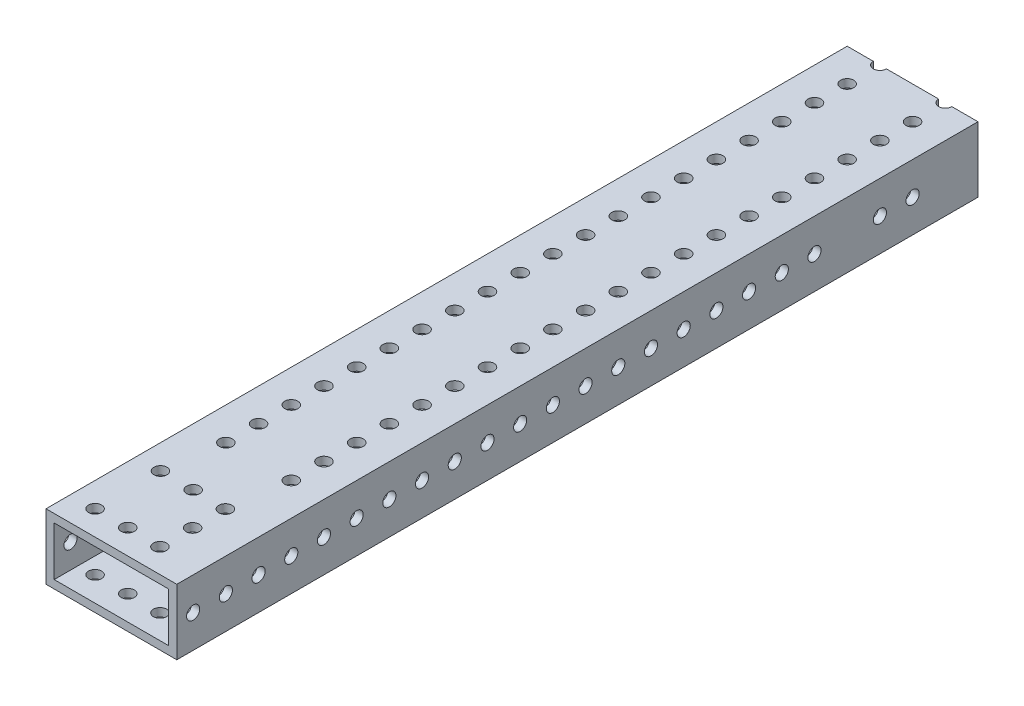
SolidWorks part; units mm, degrees
material "6061-T6 (SS)"
ref_plane "Front Plane" through (0, 0, 0) normal (0, 0, 1) x (1, 0, 0)
ref_plane "Top Plane" through (0, 0, 0) normal (0, 1, 0) x (1, 0, 0)
ref_plane "Right Plane" through (0, 0, 0) normal (1, 0, 0) x (0, 0, -1)
sketch "Sketch1" plane through (0, 0, 0) normal (0, 0, 1) x (1, 0, 0)
  line L0 (-22.225, 9.525) -> (22.225, 9.525)
  line L1 (-25.4, 12.7) -> (25.4, 12.7)
  line L2 (-25.4, 12.7) -> (-25.4, -12.7)
  line L3 (-25.4, -12.7) -> (25.4, -12.7)
  line L4 (25.4, 12.7) -> (25.4, -12.7)
  line L5 (22.225, 9.525) -> (22.225, -9.525)
  line L6 (-22.225, -9.525) -> (22.225, -9.525)
  line L7 (-22.225, 9.525) -> (-22.225, -9.525)
  line L8 (-25.4, 12.7) -> (25.4, -12.7) construction
  line L9 (25.4, 12.7) -> (-25.4, -12.7) construction
  point P5 (0, 0)
  dimension "D1" = 50.8
  dimension "D2" = 25.4
  dimension "D3" = 3.175
extrude "Boss-Extrude1" add sketch "Sketch1" along normal mid plane 469.9
sketch "Sketch5" plane through (-25.4, 0, 0) normal (-1, 0, 0) x (0, 0, 1)
  line L0 (234.95, -12.7) -> (-234.95, -12.7) construction
  line L1 (-234.95, 12.7) -> (-171.45, 12.7)
  line L2 (-234.95, 12.7) -> (-234.95, -12.7)
  line L3 (-234.95, -12.7) -> (-171.45, -12.7)
  line L4 (-171.45, 12.7) -> (-171.45, -12.7)
  dimension "D1" = 63.5
sketch "Sketch6" plane through (25.4, 0, 0) normal (1, 0, 0) x (0, 0, -1)
  line L0 (-234.95, -12.7) -> (-234.95, 12.7) construction
  line L1 (-234.95, 12.7) -> (234.95, 12.7) construction
  circle A0 centre (-228.6, 0) radius 2.5527
  circle A1 centre (-215.9, 0) radius 2.5527
  circle A2 centre (-203.2, 0) radius 2.5527
  circle A3 centre (-190.5, 0) radius 2.5527
  circle A4 centre (-177.8, 0) radius 2.5527
  circle A5 centre (-165.1, 0) radius 2.5527
  circle A6 centre (-152.4, 0) radius 2.5527
  circle A7 centre (-139.7, 0) radius 2.5527
  circle A8 centre (-127, 0) radius 2.5527
  circle A9 centre (-114.3, 0) radius 2.5527
  circle A10 centre (-101.6, 0) radius 2.5527
  circle A11 centre (-88.9, 0) radius 2.5527
  circle A12 centre (-76.2, 0) radius 2.5527
  circle A13 centre (-63.5, 0) radius 2.5527
  circle A14 centre (-50.8, 0) radius 2.5527
  circle A15 centre (-38.1, 0) radius 2.5527
  circle A16 centre (-25.4, 0) radius 2.5527
  circle A17 centre (-12.7, 0) radius 2.5527
  circle A18 centre (0, 0) radius 2.5527
  circle A19 centre (12.7, 0) radius 2.5527
  circle A20 centre (25.4, 0) radius 2.5527 construction
  circle A21 centre (38.1, 0) radius 2.5527
  circle A22 centre (50.8, 0) radius 2.5527
  circle A23 centre (63.5, 0) radius 2.5527 construction
  circle A24 centre (76.2, 0) radius 2.5527 construction
  circle A25 centre (88.9, 0) radius 2.5527 construction
  circle A26 centre (101.6, 0) radius 2.5527 construction
  circle A27 centre (114.3, 0) radius 2.5527 construction
  circle A28 centre (127, 0) radius 2.5527 construction
  dimension "D1" = 6.35
  dimension "D2" = 12.7
  dimension "D3" = 5.1054
  dimension "D4" = 29
extrude "Cut-Extrude5" cut sketch "Sketch6" against normal through all
extrude "Cut-Extrude6" cut sketch "Sketch5" against normal through all
sketch "Sketch2" plane through (0, 12.7, 0) normal (0, 1, 0) x (1, 0, 0)
  line L0 (25.4, -234.95) -> (-25.4, -234.95) construction
  line L1 (-25.4, -234.95) -> (-25.4, 171.45) construction
  line L2 (-25.4, -234.95) -> (-25.4, 171.45) construction
  line L3 (25.4, -234.95) -> (25.4, 171.45) construction
  line L4 (25.4, 184.15) -> (-25.4, 184.15) construction
  circle A0 centre (12.7, -228.6) radius 2.5527 construction
  circle A1 centre (25.4, -171.45) radius 2.5527 construction
  circle A2 centre (-12.7, -228.6) radius 2.5527 construction
  circle A3 centre (-12.7, -215.9) radius 2.5527 construction
  circle A4 centre (12.7, -215.9) radius 2.5527 construction
  circle A5 centre (25.4, -158.75) radius 2.5527 construction
  circle A6 centre (-12.7, -203.2) radius 2.5527 construction
  circle A7 centre (12.7, -203.2) radius 2.5527 construction
  circle A8 centre (25.4, -146.05) radius 2.5527 construction
  circle A9 centre (-12.7, -190.5) radius 2.5527 construction
  circle A10 centre (12.7, -190.5) radius 2.5527 construction
  circle A11 centre (25.4, -133.35) radius 2.5527 construction
  circle A12 centre (-12.7, -177.8) radius 2.5527
  circle A13 centre (12.7, -177.8) radius 2.5527 construction
  circle A14 centre (25.4, -120.65) radius 2.5527 construction
  circle A15 centre (-12.7, -165.1) radius 2.5527
  circle A16 centre (12.7, -165.1) radius 2.5527 construction
  circle A17 centre (25.4, -107.95) radius 2.5527 construction
  circle A18 centre (-12.7, -152.4) radius 2.5527
  circle A19 centre (12.7, -152.4) radius 2.5527 construction
  circle A20 centre (25.4, -95.25) radius 2.5527 construction
  circle A21 centre (-12.7, -139.7) radius 2.5527
  circle A22 centre (12.7, -139.7) radius 2.5527 construction
  circle A23 centre (25.4, -82.55) radius 2.5527 construction
  circle A24 centre (-12.7, -127) radius 2.5527
  circle A25 centre (12.7, -127) radius 2.5527 construction
  circle A26 centre (25.4, -69.85) radius 2.5527 construction
  circle A27 centre (-12.7, -114.3) radius 2.5527
  circle A28 centre (12.7, -114.3) radius 2.5527 construction
  circle A29 centre (25.4, -57.15) radius 2.5527 construction
  circle A30 centre (-12.7, -101.6) radius 2.5527
  circle A31 centre (12.7, -101.6) radius 2.5527 construction
  circle A32 centre (25.4, -44.45) radius 2.5527 construction
  circle A33 centre (-12.7, -88.9) radius 2.5527
  circle A34 centre (12.7, -88.9) radius 2.5527 construction
  circle A35 centre (25.4, -31.75) radius 2.5527 construction
  circle A36 centre (-12.7, -76.2) radius 2.5527
  circle A37 centre (12.7, -76.2) radius 2.5527 construction
  circle A38 centre (25.4, -19.05) radius 2.5527 construction
  circle A39 centre (-12.7, -63.5) radius 2.5527
  circle A40 centre (12.7, -63.5) radius 2.5527 construction
  circle A41 centre (25.4, -6.35) radius 2.5527 construction
  circle A42 centre (-12.7, -50.8) radius 2.5527
  circle A43 centre (12.7, -50.8) radius 2.5527 construction
  circle A44 centre (25.4, 6.35) radius 2.5527 construction
  circle A45 centre (-12.7, -38.1) radius 2.5527
  circle A46 centre (12.7, -38.1) radius 2.5527 construction
  circle A47 centre (25.4, 19.05) radius 2.5527 construction
  circle A48 centre (-12.7, -25.4) radius 2.5527
  circle A49 centre (12.7, -25.4) radius 2.5527 construction
  circle A50 centre (25.4, 31.75) radius 2.5527 construction
  circle A51 centre (-12.7, -12.7) radius 2.5527
  circle A52 centre (12.7, -12.7) radius 2.5527 construction
  circle A53 centre (25.4, 44.45) radius 2.5527 construction
  circle A54 centre (-12.7, 0) radius 2.5527
  circle A55 centre (12.7, 0) radius 2.5527 construction
  circle A56 centre (25.4, 57.15) radius 2.5527 construction
  circle A57 centre (-12.7, 12.7) radius 2.5527
  circle A58 centre (12.7, 12.7) radius 2.5527 construction
  circle A59 centre (25.4, 69.85) radius 2.5527 construction
  circle A60 centre (-12.7, 25.4) radius 2.5527
  circle A61 centre (12.7, 25.4) radius 2.5527
  circle A62 centre (25.4, 82.55) radius 2.5527 construction
  circle A63 centre (-12.7, 38.1) radius 2.5527
  circle A64 centre (12.7, 38.1) radius 2.5527 construction
  circle A65 centre (25.4, 95.25) radius 2.5527 construction
  circle A66 centre (-12.7, 50.8) radius 2.5527
  circle A67 centre (12.7, 50.8) radius 2.5527 construction
  circle A68 centre (25.4, 107.95) radius 2.5527 construction
  circle A69 centre (-12.7, 63.5) radius 2.5527
  circle A70 centre (12.7, 63.5) radius 2.5527
  circle A71 centre (25.4, 120.65) radius 2.5527 construction
  circle A72 centre (-12.7, 76.2) radius 2.5527
  circle A73 centre (12.7, 76.2) radius 2.5527
  circle A74 centre (25.4, 133.35) radius 2.5527 construction
  circle A75 centre (-12.7, 88.9) radius 2.5527
  circle A76 centre (12.7, 88.9) radius 2.5527 construction
  circle A77 centre (25.4, 146.05) radius 2.5527 construction
  circle A78 centre (-12.7, 101.6) radius 2.5527
  circle A79 centre (12.7, 101.6) radius 2.5527 construction
  circle A80 centre (25.4, 158.75) radius 2.5527 construction
  circle A81 centre (-12.7, 114.3) radius 2.5527
  circle A82 centre (12.7, 114.3) radius 2.5527 construction
  circle A83 centre (25.4, 171.45) radius 2.5527 construction
  circle A84 centre (-12.7, 127) radius 2.5527 construction
  circle A85 centre (12.7, 127) radius 2.5527 construction
  circle A86 centre (25.4, 184.15) radius 2.5527 construction
  circle A87 centre (-12.7, 139.7) radius 2.5527
  circle A88 centre (12.7, 139.7) radius 2.5527 construction
  circle A89 centre (25.4, 196.85) radius 2.5527 construction
  circle A90 centre (-12.7, 152.4) radius 2.5527
  circle A91 centre (12.7, 152.4) radius 2.5527 construction
  circle A92 centre (25.4, 209.55) radius 2.5527 construction
  circle A93 centre (-12.7, 165.1) radius 2.5527
  circle A94 centre (12.7, 165.1) radius 2.5527 construction
  circle A95 centre (25.4, 222.25) radius 2.5527 construction
  circle A96 centre (-12.7, 177.8) radius 2.5527
  circle A97 centre (12.7, 177.8) radius 2.5527 construction
  circle A98 centre (25.4, 234.95) radius 2.5527 construction
  circle A99 centre (-12.7, 190.5) radius 2.5527
  circle A100 centre (12.7, 190.5) radius 2.5527 construction
  circle A101 centre (25.4, 247.65) radius 2.5527 construction
  circle A108 centre (-12.7, 215.9) radius 2.5527 [skipped]
  circle A109 centre (12.7, 215.9) radius 2.5527 [skipped]
  circle A110 centre (25.4, 273.05) radius 2.5527 [skipped]
  circle A111 centre (-12.7, 203.2) radius 2.5527 [skipped]
  circle A112 centre (12.7, 203.2) radius 2.5527 [skipped]
  circle A113 centre (25.4, 260.35) radius 2.5527 [skipped]
  circle A114 centre (25.4, 260.35) radius 2.5527 construction
  circle A115 centre (12.7, 203.2) radius 2.5527 construction
  circle A116 centre (-12.7, 203.2) radius 2.5527
  circle A117 centre (25.4, 273.05) radius 2.5527 construction
  circle A118 centre (12.7, 215.9) radius 2.5527 construction
  circle A119 centre (-12.7, 215.9) radius 2.5527
  circle A120 centre (25.4, 285.75) radius 2.5527 construction
  circle A121 centre (12.7, 228.6) radius 2.5527 construction
  circle A122 centre (-12.7, 228.6) radius 2.5527
  circle A123 centre (25.4, 298.45) radius 2.5527 construction
  circle A124 centre (12.7, 241.3) radius 2.5527 construction
  circle A125 centre (-12.7, 241.3) radius 2.5527
  circle A126 centre (25.4, 311.15) radius 2.5527 construction
  circle A127 centre (12.7, 254) radius 2.5527 construction
  circle A128 centre (-12.7, 254) radius 2.5527
  circle A129 centre (25.4, 323.85) radius 2.5527 construction
  circle A130 centre (12.7, 266.7) radius 2.5527 construction
  circle A131 centre (-12.7, 266.7) radius 2.5527
  circle A132 centre (25.4, 336.55) radius 2.5527 construction
  circle A133 centre (12.7, 279.4) radius 2.5527 construction
  circle A134 centre (-12.7, 279.4) radius 2.5527
  circle A135 centre (25.4, 349.25) radius 2.5527 construction
  circle A136 centre (12.7, 292.1) radius 2.5527 construction
  circle A137 centre (-12.7, 292.1) radius 2.5527
  circle A138 centre (25.4, 361.95) radius 2.5527 construction
  circle A139 centre (12.7, 304.8) radius 2.5527 construction
  circle A140 centre (-12.7, 304.8) radius 2.5527
  circle A141 centre (25.4, 374.65) radius 2.5527 construction
  circle A142 centre (12.7, 317.5) radius 2.5527 construction
  circle A143 centre (-12.7, 317.5) radius 2.5527
  circle A144 centre (25.4, 387.35) radius 2.5527 construction
  circle A145 centre (12.7, 330.2) radius 2.5527 construction
  circle A146 centre (-12.7, 330.2) radius 2.5527
  circle A147 centre (25.4, 400.05) radius 2.5527 construction
  circle A148 centre (12.7, 342.9) radius 2.5527 construction
  circle A149 centre (-12.7, 342.9) radius 2.5527
  circle A150 centre (25.4, 412.75) radius 2.5527 construction
  circle A151 centre (12.7, 355.6) radius 2.5527 construction
  circle A152 centre (-12.7, 355.6) radius 2.5527
  circle A153 centre (12.7, -215.9) radius 2.5527 construction
  circle A154 centre (12.7, -203.2) radius 2.5527 construction
  circle A155 centre (12.7, -190.5) radius 2.5527 construction
  circle A156 centre (12.7, -177.8) radius 2.5527
  circle A157 centre (12.7, -165.1) radius 2.5527
  circle A158 centre (12.7, -152.4) radius 2.5527
  circle A159 centre (12.7, -139.7) radius 2.5527
  circle A160 centre (12.7, -127) radius 2.5527
  circle A161 centre (12.7, -114.3) radius 2.5527
  circle A162 centre (12.7, -101.6) radius 2.5527
  circle A163 centre (12.7, -88.9) radius 2.5527
  circle A164 centre (12.7, -76.2) radius 2.5527
  circle A165 centre (12.7, -63.5) radius 2.5527
  circle A166 centre (12.7, -50.8) radius 2.5527
  circle A167 centre (12.7, -38.1) radius 2.5527
  circle A168 centre (12.7, -25.4) radius 2.5527
  circle A169 centre (12.7, -12.7) radius 2.5527
  circle A170 centre (12.7, 0) radius 2.5527
  circle A171 centre (12.7, 12.7) radius 2.5527
  circle A172 centre (12.7, 25.4) radius 2.5527 construction
  circle A173 centre (12.7, 38.1) radius 2.5527
  circle A174 centre (12.7, 50.8) radius 2.5527
  circle A175 centre (12.7, 63.5) radius 2.5527 construction
  circle A176 centre (12.7, 76.2) radius 2.5527 construction
  circle A177 centre (12.7, 88.9) radius 2.5527
  circle A178 centre (12.7, 101.6) radius 2.5527
  circle A179 centre (12.7, 114.3) radius 2.5527
  circle A180 centre (12.7, 127) radius 2.5527 construction
  circle A181 centre (12.7, 139.7) radius 2.5527
  circle A182 centre (12.7, 152.4) radius 2.5527
  circle A183 centre (12.7, 165.1) radius 2.5527
  circle A184 centre (12.7, 177.8) radius 2.5527
  circle A185 centre (12.7, 190.5) radius 2.5527
  circle A186 centre (12.7, 203.2) radius 2.5527
  circle A187 centre (12.7, 215.9) radius 2.5527
  circle A188 centre (12.7, 228.6) radius 2.5527
  circle A189 centre (12.7, 241.3) radius 2.5527
  circle A190 centre (12.7, 254) radius 2.5527
  circle A191 centre (12.7, 266.7) radius 2.5527
  circle A192 centre (12.7, 279.4) radius 2.5527
  circle A193 centre (12.7, 292.1) radius 2.5527
  circle A194 centre (12.7, 304.8) radius 2.5527
  circle A195 centre (12.7, 317.5) radius 2.5527
  circle A196 centre (12.7, 330.2) radius 2.5527
  circle A197 centre (12.7, 342.9) radius 2.5527
  circle A198 centre (12.7, 355.6) radius 2.5527
  circle A199 centre (12.7, 368.3) radius 2.5527
  circle A200 centre (12.7, 381) radius 2.5527
  circle A201 centre (12.7, 393.7) radius 2.5527
  circle A202 centre (-15.875, -225.425) radius 2.5527
  circle A206 centre (-15.875, -200.025) radius 2.5527
  circle A207 centre (-3.175, -200.025) radius 2.5527
  circle A208 centre (-3.175, -225.425) radius 2.5527
  circle A210 centre (9.525, -225.6155) radius 2.5527
  circle A211 centre (9.525, -212.9155) radius 2.5527
  circle A212 centre (9.525, -200.2155) radius 2.5527
  dimension "D2" = 5.1054
  dimension "D4" = 50
  dimension "D9" = 12.7
  dimension "D10" = 12.7
  dimension "D11" = 6.35
  dimension "D12" = 5.1054
  dimension "D13" = 9.525
  dimension "D14" = 9.525
  dimension "D17" = 25.4
  dimension "D18" = 9.525
  dimension "D19" = 28.575
  dimension "D20" = 15.875
  dimension "D21" = 9.3345
  dimension "D22" = 5.1054
  dimension "D24" = 12.7
  dimension "D1" = 6.35
  dimension "D3" = 38.1
  dimension "D6" = 12.7
  dimension "D7" = 6.35
  dimension "D5" = 36
  dimension "D8" = 14
  dimension "D15" = 2
  dimension "D16" = 2
  dimension "D23" = 3
extrude "Cut-Extrude1" cut sketch "Sketch2" against normal through all
sketch "Sketch7" plane through (-25.4, 0, 0) normal (-1, 0, 0) x (0, 0, 1)
  line L5 (-171.45, 12.7) -> (-76.2, 12.7)
  line L6 (-171.45, 12.7) -> (-171.45, -12.7)
  line L7 (-171.45, -12.7) -> (-76.2, -12.7)
  line L8 (-76.2, 12.7) -> (-76.2, -12.7)
  dimension "D1" = 95.25
extrude "Cut-Extrude7" cut sketch "Sketch7" against normal through all
